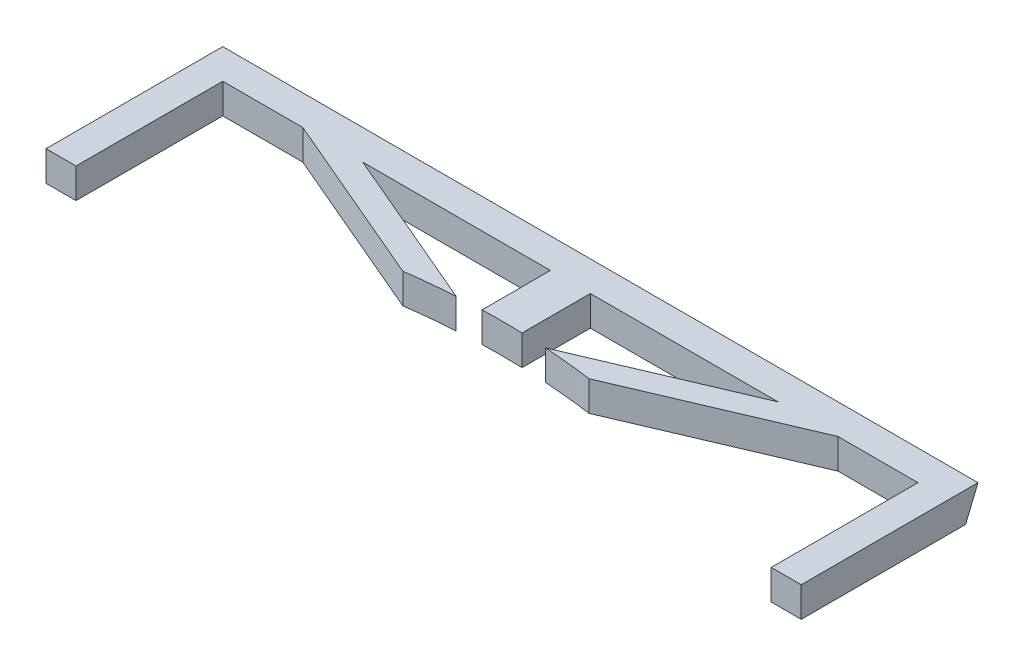
SolidWorks part; units mm, degrees
ref_plane "Front Plane" through (0, 0, 0) normal (0, 0, 1) x (1, 0, 0)
ref_plane "Top Plane" through (0, 0, 0) normal (0, 1, 0) x (1, 0, 0)
ref_plane "Right Plane" through (0, 0, 0) normal (1, 0, 0) x (0, 0, -1)
sketch "Sketch1" plane through (0, 0, 0) normal (0, 1, 0) x (1, 0, 0)
  line L0 (-119.8562, 0) -> (119.8562, 0)
  line L1 (-119.8562, 0) -> (-119.8562, -56.1003)
  line L2 (119.8562, 0) -> (119.8563, -56.1003)
  line L3 (-119.8562, -56.1003) -> (-100.8062, -56.1003)
  line L4 (119.8563, -56.1003) -> (100.8063, -56.1003)
  line L6 (-119.8563, -56.1003) -> (-100.8063, -56.1003) construction
  arc A1 (-100.8062, -56.1003) -> (100.8063, -56.1003) centre (0, -247.0215) cw
  point P2 (0, 0)
  dimension "D3" = 215.9
  dimension "D1" = 239.7125
  dimension "D4" = 19.05
  dimension "D5" = 19.05
extrude "Boss-Extrude1" add sketch "Sketch1" along normal blind 9.525
chamfer "Chamfer1" distance 3.9348 distance2 9.525 1 edges at (0, 0, 0) first distance on face at (0, 0, 33.237)
sketch "Sketch3" plane through (0, 9.525, 0) normal (0, 1, 0) x (1, 0, 0)
  line L0 (-110.3312, -58.6915) -> (-110.3312, -9.525)
  line L1 (-110.3312, -9.525) -> (-84.9312, -9.525)
  line L3 (-119.8562, 0) -> (-119.8562, -56.1003) construction
  line L4 (119.8562, 0) -> (-119.8562, 0) construction
  line L5 (-84.9312, -9.525) -> (-25.4, -34.925)
  line L7 (-65.8812, -9.525) -> (-6.35, -34.925)
  line L8 (-6.35, -34.925) -> (-6.35, -9.525)
  line L9 (-6.35, -9.525) -> (-65.8812, -9.525)
  line L10 (0, 0) -> (0, -31.1215) construction
  line L17 (-110.3312, -58.6915) -> (-100.8063, -58.6915)
  line L18 (110.3313, -58.6915) -> (100.8063, -58.6915)
  line L19 (6.35, -9.525) -> (65.8812, -9.525)
  line L20 (6.35, -34.925) -> (6.35, -9.525)
  line L21 (65.8812, -9.525) -> (6.35, -34.925)
  line L22 (84.9312, -9.525) -> (25.4, -34.925)
  line L23 (110.3312, -9.525) -> (84.9312, -9.525)
  line L24 (110.3313, -58.6915) -> (110.3312, -9.525)
  arc A7 (-100.8063, -58.6915) -> (-25.4, -34.925) centre (0, -247.0215) cw
  arc A8 (100.8063, -56.1003) -> (-100.8063, -56.1003) centre (0, -247.0215) ccw construction
  arc A9 (100.8063, -58.6915) -> (25.4, -34.925) centre (0, -247.0215) ccw
  dimension "D1" = 9.525
  dimension "D3" = 12.7
  dimension "D6" = 25.4
  dimension "D2" = 9.525
  dimension "D4" = 19.05
  dimension "D5" = 25.4
extrude "Cut-Extrude1" cut sketch "Sketch3" against normal through all
